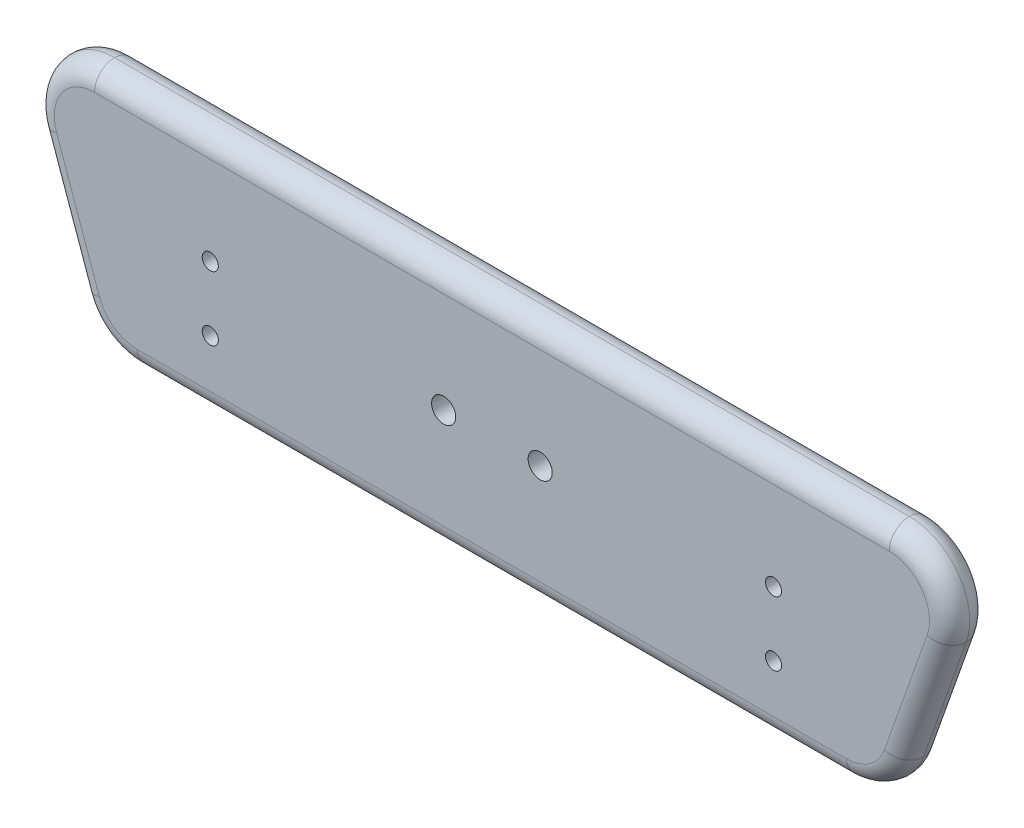
SolidWorks part; units mm, degrees
ref_plane "前基準面" through (0, 0, 0) normal (0, 0, 1) x (1, 0, 0)
ref_plane "上基準面" through (0, 0, 0) normal (0, 1, 0) x (1, 0, 0)
ref_plane "右基準面" through (0, 0, 0) normal (1, 0, 0) x (0, 0, -1)
sketch "草圖1" plane through (0, 0, 0) normal (0, 0, 1) x (1, 0, 0)
  line L0 (-123.9462, 3.4978) -> (-102.6991, -56.5022)
  line L1 (-123.9462, 3.4978) -> (116.0538, 3.4978)
  line L3 (-102.6991, -56.5022) -> (94.8067, -56.5022)
  line L5 (116.0538, 3.4978) -> (94.8067, -56.5022)
  dimension "D1" = 240
  dimension "D3" = 70.5
  dimension "D4" = 70.5
extrude "填料-伸長1" add sketch "草圖1" along normal blind 10
fillet "圓角1" radius 15 4 edges at (116.0538, 3.4978, 5) (94.8067, -56.5022, 5) (-102.6991, -56.5022, 5) (-123.9462, 3.4978, 5)
fillet "圓角2" radius 5 16 edges at (107.0789, -2.8451, 10) (103.6571, -31.5093, 10) (92.8629, -53.7519, 10) (-3.9462, -56.5022, 10) (-100.7553, -53.7519, 10) (-111.5495, -31.5093, 10) (-114.9713, -2.8451, 10) (-3.9462, 3.4978, 10) (-114.9713, -2.8451, 0) (-111.5495, -31.5093, 0) (-100.7553, -53.7519, 0) (-3.9462, -56.5022, 0) (92.8629, -53.7519, 0) (103.6571, -31.5093, 0) (107.0789, -2.8451, 0) (-3.9462, 3.4978, 0)
sketch "草圖2" plane through (0, 0, 10) normal (0, 0, 1) x (1, 0, 0)
  circle A0 centre (-73.9462, -23.5022) radius 2
  circle A1 centre (-73.9462, -39.5022) radius 2
  circle A2 centre (66.0538, -39.5022) radius 2
  circle A3 centre (66.0538, -23.5022) radius 2
  dimension "D3" = 16
extrude "除料-伸長1" cut sketch "草圖2" against normal blind 7.5
sketch "草圖3" plane through (0, 0, 0) normal (0, 0, -1) x (-1, 0, 0)
  line L0 (3.9462, 3.4978) -> (3.9462, -6.5022) construction
  line L2 (-94.8293, 3.4978) -> (102.7217, 3.4978) construction
  line L4 (-19.0538, -46.5022) -> (26.9462, -46.5022)
  line L5 (-19.0538, -46.5022) -> (-19.0538, -6.5022)
  line L6 (-19.0538, -6.5022) -> (26.9462, -6.5022)
  line L7 (26.9462, -46.5022) -> (26.9462, -6.5022)
  dimension "D2" = 40
  dimension "D3" = 46
extrude "除料-伸長2" cut sketch "草圖3" against normal blind 4 contours L5 L4 L7 L6
sketch "草圖8" plane through (0, 0, 4) normal (0, 0, -1) x (-1, 0, 0)
  line L0 (3.9462, 3.4978) -> (3.9462, -26.5022)
  line L1 (-94.8293, 3.4978) -> (102.7217, 3.4978) construction
  line L2 (3.9462, -26.5022) -> (15.9462, -26.5022)
  circle A0 centre (15.9462, -26.5022) radius 3
  circle A1 centre (-8.0538, -26.5022) radius 3
  dimension "D3" = 6
  dimension "D1" = 30
  dimension "D2" = 12
extrude "除料-伸長3" cut sketch "草圖8" against normal through all contours A0 | A1
